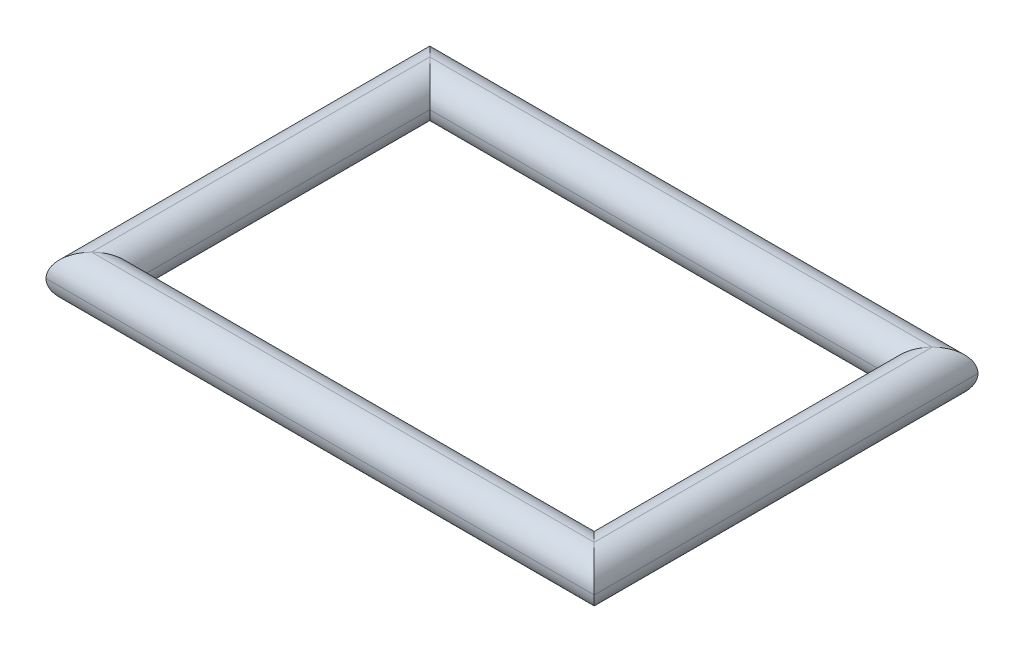
SolidWorks part; units mm, degrees
ref_plane "Front Plane" through (0, 0, 0) normal (0, 0, 1) x (1, 0, 0)
ref_plane "Top Plane" through (0, 0, 0) normal (0, 1, 0) x (1, 0, 0)
ref_plane "Right Plane" through (0, 0, 0) normal (1, 0, 0) x (0, 0, -1)
sketch "Sketch1" plane through (0, 0, 0) normal (0, 1, 0) x (1, 0, 0)
  line L1 (-33.0189, 25.4717) -> (26.9811, 25.4717)
  line L2 (-33.0189, 25.4717) -> (-33.0189, -16.5283)
  line L3 (-33.0189, -16.5283) -> (26.9811, -16.5283)
  line L4 (26.9811, 25.4717) -> (26.9811, -16.5283)
  dimension "D1" = 60
  dimension "D2" = 42
extrude "Boss-Extrude1" add sketch "Sketch1" along normal blind 5 contours L2 L3 L4 L1
sketch "Sketch2" plane through (0, 5, 0) normal (0, 1, 0) x (1, 0, 0)
  line L0 (-33.0189, 25.4717) -> (26.9811, 25.4717) construction
  line L1 (-28.0189, 20.4717) -> (21.9811, 20.4717)
  line L2 (-28.0189, 20.4717) -> (-28.0189, -11.5283)
  line L3 (-28.0189, -11.5283) -> (21.9811, -11.5283)
  line L4 (21.9811, 20.4717) -> (21.9811, -11.5283)
  line L5 (-33.0189, 25.4717) -> (-33.0189, -16.5283) construction
  line L6 (-33.0189, -16.5283) -> (26.9811, -16.5283) construction
  line L7 (26.9811, 25.4717) -> (26.9811, -16.5283) construction
  dimension "D1" = 5
  dimension "D2" = 5
  dimension "D3" = 5
  dimension "D4" = 5
extrude "Cut-Extrude1" cut sketch "Sketch2" against normal blind 5
fillet "Fillet1" radius 2.5 8 edges at (26.9811, 5, -4.4717) (-3.0189, 5, 16.5283) (-33.0189, 5, -4.4717) (-3.0189, 5, -25.4717) (21.9811, 5, -4.4717) (-3.0189, 5, -20.4717) (-28.0189, 5, -4.4717) (-3.0189, 5, 11.5283)
fillet "Fillet2" radius 2.5 8 edges at (-33.0189, 0, -4.4717) (-3.0189, 0, 16.5283) (26.9811, 0, -4.4717) (-3.0189, 0, -25.4717) (-3.0189, 0, -20.4717) (21.9811, 0, -4.4717) (-3.0189, 0, 11.5283) (-28.0189, 0, -4.4717)
